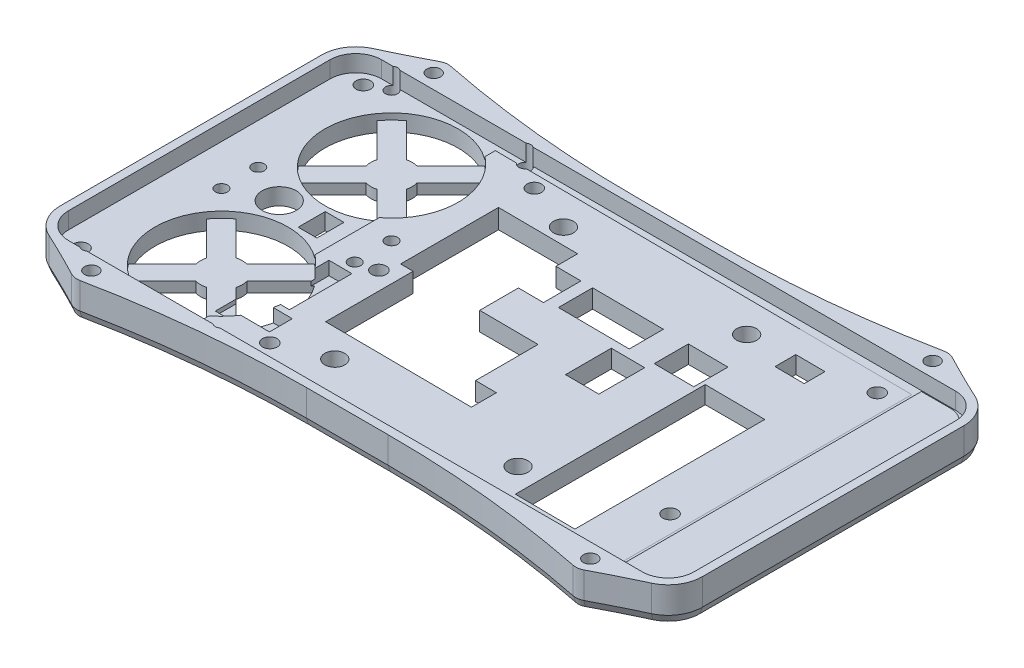
SolidWorks part; units mm, degrees
ref_plane "前视基准面" through (0, 0, 0) normal (0, 0, 1) x (1, 0, 0)
ref_plane "上视基准面" through (0, 0, 0) normal (0, 1, 0) x (1, 0, 0)
ref_plane "右视基准面" through (0, 0, 0) normal (1, 0, 0) x (0, 0, -1)
sketch "草图1" plane through (0, 0, 0) normal (0, 1, 0) x (1, 0, 0)
  line L0 (6, 0.2) -> (143.8, 0.2)
  line L1 (6, 0) -> (143.8, 0) construction
  line L2 (0, -6) -> (0, -68.8) construction
  line L3 (6, -74.8) -> (143.8, -74.8) construction
  line L4 (149.8, -6) -> (149.8, -68.8) construction
  line L5 (150, -6) -> (150, -68.8)
  line L6 (6, -75) -> (143.8, -75)
  line L7 (-0.2, -6) -> (-0.2, -68.8)
  arc A0 (143.8, 0) -> (149.8, -6) centre (143.8, -6) cw construction
  arc A1 (143.8, -74.8) -> (149.8, -68.8) centre (143.8, -68.8) ccw construction
  arc A2 (0, -68.8) -> (6, -74.8) centre (6, -68.8) ccw construction
  arc A3 (6, 0) -> (0, -6) centre (6, -6) ccw construction
  arc A4 (143.8, 0.2) -> (150, -6) centre (143.8, -6) cw
  arc A5 (143.8, -75) -> (150, -68.8) centre (143.8, -68.8) ccw
  arc A6 (-0.2, -68.8) -> (6, -75) centre (6, -68.8) ccw
  arc A7 (6, 0.2) -> (-0.2, -6) centre (6, -6) ccw
  point P7 (149.8, 0)
  point P12 (0, -74.8)
  point P15 (0, 0)
  dimension "D3" = 6
  dimension "D1" = 74.8
  dimension "D2" = 149.8
  dimension "D4" = 0.2
extrude "凸台-拉伸1" add sketch "草图1" along normal blind 4
sketch "草图2" plane through (0, 0, 0) normal (0, -1, 0) x (-1, 0, 0)
  line L0 (-122.6, -55.35) -> (-108.9, -55.35)
  line L1 (-122.6, -69.85) -> (-108.9, -69.85)
  line L2 (-122.6, -69.85) -> (-122.6, -63.95)
  line L3 (-122.6, -63.95) -> (-108.9, -63.95)
  line L4 (-108.9, -69.85) -> (-108.9, -63.95)
  line L5 (-135.3, -1.25) -> (-35.3, -1.25) construction
  line L6 (-135.3, -1.25) -> (-135.3, -73.55) construction
  line L7 (-135.3, -73.55) -> (-35.3, -73.55) construction
  line L8 (-35.3, -1.25) -> (-35.3, -73.55) construction
  line L9 (-108.9, -61.25) -> (-108.9, -55.35)
  line L10 (-122.6, -61.25) -> (-108.9, -61.25)
  line L11 (-122.6, -61.25) -> (-122.6, -55.35)
  line L12 (-122.6, -46.75) -> (-108.9, -46.75)
  line L13 (-108.9, -52.65) -> (-108.9, -46.75)
  line L14 (-122.6, -52.65) -> (-108.9, -52.65)
  line L15 (-122.6, -52.65) -> (-122.6, -46.75)
  line L16 (-122.6, -38.15) -> (-108.9, -38.15)
  line L17 (-108.9, -44.05) -> (-108.9, -38.15)
  line L18 (-122.6, -44.05) -> (-108.9, -44.05)
  line L19 (-122.6, -44.05) -> (-122.6, -38.15)
  line L20 (0, -6) -> (0, -68.8) construction
  line L21 (-35.3, -73.55) -> (-0.8, -73.55) construction
  line L22 (-120.25, -26.65) -> (-111.25, -26.65) construction
  line L23 (-120.25, -26.65) -> (-120.25, -33.15) construction
  line L24 (-120.25, -33.15) -> (-111.25, -33.15) construction
  line L25 (-111.25, -26.65) -> (-111.25, -33.15) construction
  line L26 (-85.8, -48.75) -> (-81.1, -48.75) construction
  line L27 (-85.8, -48.75) -> (-85.8, -58.15) construction
  line L28 (-85.8, -58.15) -> (-81.1, -58.15) construction
  line L29 (-81.1, -48.75) -> (-81.1, -58.15) construction
  line L30 (-71.5, -48.65) -> (-68.2, -48.65) construction
  line L31 (-71.5, -48.65) -> (-71.5, -57.55) construction
  line L32 (-71.5, -57.55) -> (-68.2, -57.55) construction
  line L33 (-68.2, -48.65) -> (-68.2, -57.55) construction
  line L34 (-43.1, -45.05) -> (-38.6, -45.05) construction
  line L35 (-43.1, -45.05) -> (-43.1, -59.05) construction
  line L36 (-43.1, -59.05) -> (-38.6, -59.05) construction
  line L37 (-38.6, -45.05) -> (-38.6, -59.05) construction
  line L38 (-45.3, -61.55) -> (-33.3, -61.55) construction
  line L39 (-45.3, -61.55) -> (-45.3, -66.05) construction
  line L40 (-45.3, -66.05) -> (-33.3, -66.05) construction
  line L41 (-33.3, -61.55) -> (-33.3, -66.05) construction
  line L42 (-0.8, -73.55) -> (-0.8, -1.25) construction
  line L43 (-0.8, -1.25) -> (-35.3, -1.25) construction
  line L44 (-149.8, -6) -> (-149.8, -68.8) construction
  line L45 (-30.8, -34.65) -> (-27.3, -34.65) construction
  line L46 (-30.8, -34.65) -> (-30.8, -40.15) construction
  line L47 (-30.8, -40.15) -> (-27.3, -40.15) construction
  line L48 (-27.3, -34.65) -> (-27.3, -40.15) construction
  line L49 (-120.75, -33.65) -> (-110.75, -33.65)
  line L50 (-110.75, -26.15) -> (-110.75, -33.65)
  line L51 (-120.75, -26.15) -> (-110.75, -26.15)
  line L52 (-120.75, -26.15) -> (-120.75, -33.65)
  line L53 (-86.3, -48.25) -> (-86.3, -58.65)
  line L54 (-86.3, -58.65) -> (-80.6, -58.65)
  line L55 (-80.6, -48.25) -> (-80.6, -58.65)
  line L56 (-86.3, -48.25) -> (-80.6, -48.25)
  line L57 (-72, -48.15) -> (-72, -58.05)
  line L58 (-72, -58.05) -> (-67.7, -58.05)
  line L59 (-67.7, -48.15) -> (-67.7, -58.05)
  line L60 (-72, -48.15) -> (-67.7, -48.15)
  line L61 (-31.3, -34.15) -> (-31.3, -40.65)
  line L62 (-31.3, -40.65) -> (-26.8, -40.65)
  line L63 (-26.8, -34.15) -> (-26.8, -40.65)
  line L64 (-31.3, -34.15) -> (-26.8, -34.15)
  line L65 (-43.6, -44.55) -> (-43.6, -59.55)
  line L66 (-43.6, -59.55) -> (-38.1, -59.55)
  line L67 (-38.1, -44.55) -> (-38.1, -59.55)
  line L68 (-43.6, -44.55) -> (-38.1, -44.55)
  line L69 (-45.8, -61.05) -> (-45.8, -66.55)
  line L70 (-45.8, -66.55) -> (-32.8, -66.55)
  line L71 (-32.8, -61.05) -> (-32.8, -66.55)
  line L72 (-45.8, -61.05) -> (-32.8, -61.05)
  circle A0 centre (-103.2, -9.35) radius 2 construction
  circle A1 centre (-103.2, -64.25) radius 2 construction
  circle A2 centre (-59.2, -64.25) radius 2 construction
  circle A3 centre (-59.2, -9.35) radius 2 construction
  circle A4 centre (-130.8, -5.6) radius 1.25 construction
  circle A5 centre (-131.1, -55.65) radius 1.25 construction
  circle A6 centre (-47.7, -4.85) radius 1.25 construction
  circle A7 centre (-48.1, -68.75) radius 1.25 construction
  circle A8 centre (-22.8, -70.3) radius 1.25 construction
  circle A9 centre (-5.05, -71.05) radius 1.25 construction
  circle A10 centre (-5.05, -3.25) radius 1.25 construction
  circle A11 centre (-19, -37.4) radius 3.6 construction
  circle A12 centre (-103.2, -9.35) radius 2.4
  circle A13 centre (-59.2, -9.35) radius 2.4
  circle A14 centre (-59.2, -64.25) radius 2.4
  circle A15 centre (-103.2, -64.25) radius 2.4
  circle A16 centre (-19, -37.4) radius 4.1
  circle A17 centre (-130.8, -5.6) radius 1.75
  circle A18 centre (-131.1, -55.65) radius 1.75
  circle A19 centre (-48.1, -68.75) radius 1.75
  circle A20 centre (-22.8, -70.3) radius 1.75
  circle A21 centre (-5.05, -71.05) radius 1.75
  circle A22 centre (-5.05, -3.25) radius 1.75
  circle A23 centre (-47.7, -4.85) radius 1.75
  circle A24 centre (-46.11, -40.57) radius 1.25 construction
  circle A25 centre (-46.11, -40.57) radius 1.75
  point P22 (0, -37.4)
  point P23 (-135.3, -37.4)
  point P28 (-115.75, -33.15)
  point P29 (-115.75, -38.15)
  point P30 (-111.25, -29.9)
  point P31 (-108.9, -41.1)
  point P79 (-0.8, -37.4)
  point P81 (-27.3, -37.4)
  dimension "D21" = 4
  dimension "D34" = 2.5
  dimension "D53" = 7.2
  dimension "D1" = 13.7
  dimension "D2" = 5.9
  dimension "D3" = 72.3
  dimension "D4" = 3.7
  dimension "D5" = 12.7
  dimension "D7" = 14.5
  dimension "D8" = 100
  dimension "D9" = 2.7
  dimension "D10" = 9
  dimension "D11" = 6.5
  dimension "D12" = 11.2
  dimension "D13" = 15.4
  dimension "D14" = 9.4
  dimension "D15" = 4.7
  dimension "D16" = 23.1
  dimension "D17" = 3.3
  dimension "D18" = 8.9
  dimension "D19" = 16
  dimension "D20" = 37.4
  dimension "D22" = 8.1
  dimension "D23" = 32.1
  dimension "D24" = 44
  dimension "D25" = 9.3
  dimension "D26" = 14
  dimension "D27" = 4.5
  dimension "D28" = 12
  dimension "D29" = 4.5
  dimension "D30" = 3.3
  dimension "D31" = 2
  dimension "D32" = 7.5
  dimension "D33" = 14.5
  dimension "D35" = 34.5
  dimension "D36" = 2
  dimension "D37" = 4.25
  dimension "D38" = 2.5
  dimension "D39" = 3.25
  dimension "D40" = 22
  dimension "D41" = 4.8
  dimension "D42" = 12.8
  dimension "D43" = 3.6
  dimension "D44" = 12.4
  dimension "D45" = 4.35
  dimension "D46" = 4.5
  dimension "D47" = 4.2
  dimension "D48" = 17.9
  dimension "D49" = 18.2
  dimension "D50" = 3.5
  dimension "D51" = 5.5
  dimension "D52" = 8.3
  dimension "D58" = 28.18
  dimension "D59" = 1.99
  dimension "D54" = 0.4
  dimension "D55" = 0.5
  dimension "D56" = 0.5
  dimension "D57" = 0.5
  dimension "D6" = 4
sketch "草图7" plane through (0, 0, -0.2) normal (0, 0, -1) x (-1, 0, 0)
  line L0 (-135.3, 4) -> (-35.3, 4.75)
  line L2 (-35.3, 4.75) -> (-35.3, 4)
  line L4 (-35.3, 4) -> (-135.3, 4)
  line L6 (-143.8, 4) -> (-6, 4) construction
  dimension "D1" = 0.75
extrude "凸台-拉伸11" add sketch "草图7" against normal offset from surface (71.2 mm away) 2 from offset 2 up to face at (74.9, 2, 75) offset against normal yes
extrude "切除-拉伸1" cut sketch "草图2" against normal blind 10 contours A12 | A13 | A14 | A15
sketch "草图3" plane through (0, 0, 0) normal (0, 1, 0) x (1, 0, 0)
  line L0 (136.8, -1) -> (136.8, -73.8)
  line L1 (143.8, 0) -> (135.8, 0) construction
  line L2 (149.8, -6) -> (149.8, -68.8) construction
  line L3 (143.8, -74.8) -> (135.8, -74.8) construction
  line L4 (135.8, 0) -> (135.8, -74.8) construction
  line L5 (6, -74.8) -> (143.8, -74.8) construction
  line L6 (135.3, -1.25) -> (135.3, -73.55) construction
  line L7 (143.8, -73.8) -> (136.8, -73.8)
  line L8 (148.8, -6) -> (148.8, -68.8)
  line L9 (143.8, -1) -> (136.8, -1)
  arc A0 (143.8, 0) -> (149.8, -6) centre (143.8, -6) cw construction
  arc A1 (149.8, -68.8) -> (143.8, -74.8) centre (143.8, -68.8) cw construction
  arc A2 (148.8, -68.8) -> (143.8, -73.8) centre (143.8, -68.8) cw
  arc A3 (143.8, -1) -> (148.8, -6) centre (143.8, -6) cw
  point P17 (149.8, 0)
  dimension "D1" = 6
  dimension "D2" = 0.5
  dimension "D3" = 1
extrude "凸台-拉伸9" add sketch "草图3" along normal offset from surface (5 mm away) 1 up to face at (85.3, 4, 37.4) offset beyond the face yes
sketch "草图4" plane through (0, 0, 0) normal (0, 1, 0) x (1, 0, 0)
  line L0 (122.9, -24.7) -> (108.6, -24.7)
  line L1 (122.6, -25) -> (108.9, -25) construction
  line L2 (122.6, -25) -> (122.6, -70) construction
  line L3 (122.6, -70) -> (108.9, -70) construction
  line L4 (108.9, -25) -> (108.9, -70) construction
  line L5 (122.6, -69.85) -> (122.6, -63.95) construction
  line L6 (108.6, -24.7) -> (108.6, -70.3)
  line L7 (108.9, -69.85) -> (108.9, -63.95) construction
  line L8 (35.3, -73) -> (135.3, -73) construction
  line L9 (80.466, -18.85) -> (96.6871, -18.85) construction
  line L10 (107.2, 11.628) -> (107.2, 24.7853) construction
  line L11 (75.2, -18.35) -> (75.2, -26.55)
  line L12 (107.7, -18.35) -> (98.2, -18.35)
  line L13 (98.2, -18.35) -> (98.2, -26.55)
  line L14 (98.2, -26.55) -> (107.7, -26.55)
  line L15 (107.7, -26.55) -> (107.7, -18.35)
  line L16 (75.2, -26.55) -> (92.2, -26.55)
  line L17 (92.2, -26.55) -> (92.2, -18.35)
  line L18 (92.2, -18.35) -> (75.2, -18.35)
  line L19 (72.4, -27.35) -> (72.4, -18.35)
  line L20 (122.9, -70.3) -> (108.6, -70.3)
  line L21 (122.9, -24.7) -> (122.9, -70.3)
  line L22 (72.4, -18.35) -> (66.4, -18.35)
  line L23 (66.4, -27.35) -> (66.4, -36.65)
  line L24 (66.4, -27.35) -> (72.4, -27.35)
  line L25 (66.4, -13.15) -> (66.4, -18.35)
  line L26 (50.4, -36.65) -> (47.4, -36.65)
  line L27 (47.4, -36.65) -> (47.4, -13.15)
  line L28 (47.4, -13.15) -> (66.4, -13.15)
  line L29 (85.4, -51.65) -> (85.4, -57.65)
  line L30 (85.4, -57.65) -> (50.4, -57.65)
  line L31 (50.4, -57.65) -> (50.4, -36.65)
  line L32 (66.4, -36.65) -> (80.4, -36.65)
  line L33 (89.9, -39.55) -> (89.9, -28.55)
  line L34 (89.9, -28.55) -> (97.9, -28.55)
  line L35 (97.9, -28.55) -> (97.9, -39.55)
  line L36 (97.9, -39.55) -> (89.9, -39.55)
  line L37 (85.4, -51.65) -> (80.4, -51.65)
  line L38 (80.4, -51.65) -> (80.4, -36.65)
  line L39 (113.2, -12.55) -> (113.2, -7.55)
  line L40 (113.2, -7.55) -> (120.2, -7.55)
  line L41 (120.2, -7.55) -> (120.2, -12.55)
  line L42 (120.2, -12.55) -> (113.2, -12.55)
  circle A0 centre (103.2, -9.35) radius 2.4 construction
  circle A1 centre (103.2, -64.25) radius 2.4 construction
  circle A2 centre (103.2, -64.25) radius 2.4
  circle A3 centre (59.2, -64.25) radius 2.4 construction
  circle A4 centre (59.2, -64.25) radius 2.4
  dimension "D7" = 9.5
  dimension "D30" = 10
  dimension "D1" = 45
  dimension "D3" = 0.3
  dimension "D2" = 3
  dimension "D4" = 0.3
  dimension "D5" = 0.3
  dimension "D6" = 0.3
  dimension "D8" = 4
  dimension "D9" = 0.5
  dimension "D10" = 0.5
  dimension "D11" = 8.2
  dimension "D12" = 9.5
  dimension "D13" = 6
  dimension "D14" = 17
  dimension "D15" = 2.8
  dimension "D16" = 9
  dimension "D17" = 6
  dimension "D18" = 19
  dimension "D19" = 5.2
  dimension "D20" = 23.5
  dimension "D21" = 19
  dimension "D22" = 35
  dimension "D23" = 21
  dimension "D24" = 2
  dimension "D25" = 11
  dimension "D26" = 0.3
  dimension "D27" = 8
  dimension "D28" = 5
  dimension "D29" = 15
  dimension "D31" = 7
  dimension "D32" = 3.2
  dimension "D33" = 5
extrude "拉伸-薄壁1" add sketch "草图1<2>" along normal blind 8 thin thin type one direction wall 2
sketch "草图1<2>" plane through (0, 0, 0) normal (0, 1, 0) x (1, 0, 0) same geometry as "草图1"
extrude "切除-拉伸2" cut sketch "草图4" along normal through all
extrude "切除-拉伸3" cut sketch "草图2<11>" against normal through all contours L61 L62 L63 L64 | A16
sketch "草图2<11>" plane through (0, 0, 0) normal (0, -1, 0) x (-1, 0, 0) same geometry as "草图2"
extrude "切除-拉伸4" cut sketch "草图2<13>" against normal through all contours A17 | A18 | A19 | A23 | A22 | A21 | A25
sketch "草图2<13>" plane through (0, 0, 0) normal (0, -1, 0) x (-1, 0, 0) same geometry as "草图2"
extrude "切除-拉伸5" cut sketch "草图2<14>" against normal through all from offset 1.5 contours L67 L66 L65 L68 | L71 L70 L69 L72 offset against normal yes
sketch "草图2<14>" plane through (0, 0, 0) normal (0, -1, 0) x (-1, 0, 0) same geometry as "草图2"
sketch "草图5" plane through (0, 0, 0) normal (0, -1, 0) x (-1, 0, 0)
  text T0 "<b>M3*6</b>" font "@Adobe 黑体 Std R" height 7
  text T1 "<b>M3*6</b>" font "@Adobe 黑体 Std R" height 7
  text T2 "<b>M3*6</b>" font "@Adobe 黑体 Std R" height 7
  text T3 "<b>M3*6</b>" font "@Adobe 黑体 Std R" height 7
extrude "切除-拉伸6" [suppressed] cut sketch "草图5" against normal blind 0.6
sketch "草图6" plane through (0, 0, 0) normal (0, 1, 0) x (1, 0, 0)
  line L1 (0, -6) -> (0, -68.8) construction
  line L2 (149.8, -6) -> (149.8, -68.8) construction
  line L4 (6, 0.2) -> (143.8, 0.2) construction
  line L5 (6, -75) -> (143.8, -75) construction
  circle A0 centre (15, 3.7) radius 1.5 construction
  circle A1 centre (15, -78.5) radius 1.5 construction
  circle A2 centre (134.8, 3.7) radius 1.5 construction
  circle A3 centre (134.8, -78.5) radius 1.5 construction
  circle A4 centre (15, 3.7) radius 3.5
  circle A5 centre (15, -78.5) radius 3.5
  circle A6 centre (134.8, 3.7) radius 3.5
  circle A7 centre (134.8, -78.5) radius 3.5
  circle A8 centre (15, 3.7) radius 1.65
  circle A9 centre (134.8, 3.7) radius 1.65
  circle A10 centre (134.8, -78.5) radius 1.65
  circle A11 centre (15, -78.5) radius 1.65
  dimension "D1" = 3
  dimension "D3" = 0.15
  dimension "D4" = 15
  dimension "D5" = 15
  dimension "D2" = 2
extrude "凸台-拉伸10" add sketch "草图6" along normal up to surface (8 mm away) up to face at (74.9, 8, 37.4)
extrude "切除-拉伸9" cut sketch "草图6<2>" along normal through all contours A8 | A9 | A10 | A11
sketch "草图6<2>" plane through (0, 0, 0) normal (0, 1, 0) x (1, 0, 0) same geometry as "草图6"
fillet "圆角1" radius 250 8 edges at (18.1623, 4, 77) (11.8377, 4, 77) (131.6377, 4, 77) (137.9623, 4, 77) (137.9623, 4, -2.2) (131.6377, 4, -2.2) (11.8377, 4, -2.2) (18.1623, 4, -2.2)
chamfer "倒角1" distance 0.6 angle 70 20 edges at (40.2731, 0, 78.2358) (14.5029, 0, 81.9645) (74.9, 0, 77) (7.988, 0, 78.8506) (109.5269, 0, 78.2358) (-0.9143, 0, 73.2083) (135.2971, 0, 81.9645) (-2.2, 0, 37.4) (141.812, 0, 78.8506) (-0.9143, 0, 1.5917) (150.7143, 0, 73.2083) (7.988, 0, -4.0506) (152, 0, 37.4) (14.5029, 0, -7.1645) (150.7143, 0, 1.5917) (40.2731, 0, -3.4358) (141.812, 0, -4.0506) (74.9, 0, -2.2) (135.2971, 0, -7.1645) (109.5269, 0, -3.4358) first distance on face at (134.8, 0, 80.15)
sketch "草图8" plane through (0, 0, 0) normal (0, -1, 0) x (1, 0, 0)
  line L0 (9.5525, 32.9807) -> (9.5525, 0.9807) construction
  line L1 (9.5525, 0.9807) -> (41.5525, 0.9807) construction
  line L2 (41.5525, 0.9807) -> (41.5525, 32.9807) construction
  line L3 (41.5525, 32.9807) -> (9.5525, 32.9807) construction
  line L4 (31.3, 37.4) -> (26.8, 37.4) construction
  line L7 (41.5525, 41.8193) -> (9.5525, 41.8193) construction
  line L8 (41.5525, 73.8193) -> (41.5525, 41.8193) construction
  line L9 (9.5525, 73.8193) -> (41.5525, 73.8193) construction
  line L10 (9.5525, 41.8193) -> (9.5525, 73.8193) construction
  circle A0 centre (41.5525, 0.9807) radius 1.45
  circle A1 centre (41.5525, 32.9807) radius 1.45
  circle A2 centre (9.5525, 32.9807) radius 1.45
  circle A3 centre (9.5525, 0.9807) radius 1.45
  circle A4 centre (9.5525, 73.8193) radius 1.45
  circle A5 centre (9.5525, 41.8193) radius 1.45
  circle A6 centre (41.5525, 41.8193) radius 1.45
  circle A7 centre (41.5525, 73.8193) radius 1.45
  point P4 (9.5525, 16.9807)
  dimension "D3" = 2.9
  dimension "D4" = 2.9
  dimension "D5" = 2.9
  dimension "D6" = 2.9
  dimension "D1" = 32
  dimension "D2" = 32
extrude "切除-拉伸10" cut sketch "草图8" against normal through all
sketch "草图9" plane through (0, 0, 0) normal (0, -1, 0) x (1, 0, 0)
  line L0 (9.5525, 32.9807) -> (41.5525, 32.9807) construction
  line L1 (41.5525, 32.9807) -> (41.5525, 0.9807) construction
  line L2 (41.5525, 0.9807) -> (9.5525, 0.9807) construction
  line L3 (9.5525, 0.9807) -> (9.5525, 32.9807) construction
  line L4 (9.5525, 32.9807) -> (41.5525, 0.9807) construction
  line L5 (41.5525, 32.9807) -> (9.5525, 0.9807) construction
  line L6 (13.088, 32.9807) -> (41.5525, 4.5163)
  line L7 (41.5525, 4.5163) -> (38.017, 0.9807)
  line L8 (38.017, 0.9807) -> (9.5525, 29.4452)
  line L9 (9.5525, 29.4452) -> (13.088, 32.9807)
  line L10 (38.017, 32.9807) -> (9.5525, 4.5163)
  line L11 (9.5525, 4.5163) -> (13.088, 0.9807)
  line L12 (13.088, 0.9807) -> (41.5525, 29.4452)
  line L13 (41.5525, 29.4452) -> (38.017, 32.9807)
  line L14 (9.5525, 0.9807) -> (41.5525, 0.9807) construction
  line L15 (31.3, 37.4) -> (26.8, 37.4) construction
  line L18 (9.5525, 73.8193) -> (41.5525, 73.8193) construction
  line L19 (9.5525, 41.8193) -> (41.5525, 73.8193) construction
  line L20 (9.5525, 73.8193) -> (9.5525, 41.8193) construction
  line L21 (41.5525, 73.8193) -> (9.5525, 73.8193) construction
  line L22 (41.5525, 41.8193) -> (41.5525, 73.8193) construction
  line L23 (9.5525, 41.8193) -> (41.5525, 41.8193) construction
  line L24 (41.5525, 45.3548) -> (38.017, 41.8193)
  line L25 (13.088, 73.8193) -> (41.5525, 45.3548)
  line L26 (9.5525, 70.2837) -> (13.088, 73.8193)
  line L27 (38.017, 41.8193) -> (9.5525, 70.2837)
  line L28 (9.5525, 45.3548) -> (13.088, 41.8193)
  line L29 (38.017, 73.8193) -> (9.5525, 45.3548)
  line L30 (41.5525, 70.2837) -> (38.017, 73.8193)
  line L31 (13.088, 41.8193) -> (41.5525, 70.2837)
  line L32 (41.5525, 41.8193) -> (9.5525, 73.8193) construction
  circle A0 centre (25.5525, 16.9807) radius 16
  circle A1 centre (25.5525, 16.9807) radius 5
  circle A2 centre (25.5525, 57.8193) radius 5
  circle A3 centre (25.5525, 57.8193) radius 16
  dimension "D2" = 10
  dimension "D4" = 5
extrude "切除-拉伸11" cut sketch "草图9" against normal blind 10 contours A1 L10 A0 L6 | A1 L6 A0 L12 | A1 L12 A0 L8 | A1 L8 A0 L10 | A3 L29 A2 L27 | A3 L25 A2 L29 | A3 L31 A2 L25 | A3 L27 A2 L31 region at (25.5525, 0, 28.2322) region at (14.301, 0, 16.9807) region at (36.804, 0, 16.9807) region at (25.5525, 0, 5.7292) region at (36.804, 0, 57.8193) region at (25.5525, 0, 46.5678) region at (14.301, 0, 57.8193) region at (25.5525, 0, 69.0708)
sketch "草图10" plane through (0, 4, 0) normal (0, 1, 0) x (1, 0, 0)
  circle A0 centre (25.5525, -16.9807) radius 16
  circle A1 centre (25.5525, -57.8193) radius 16
  dimension "D1" = 32
  dimension "D2" = 32
extrude "切除-拉伸12" cut sketch "草图10" against normal mid plane 3
equation "\"D1@草图3\"=\"D3@草图1\""
